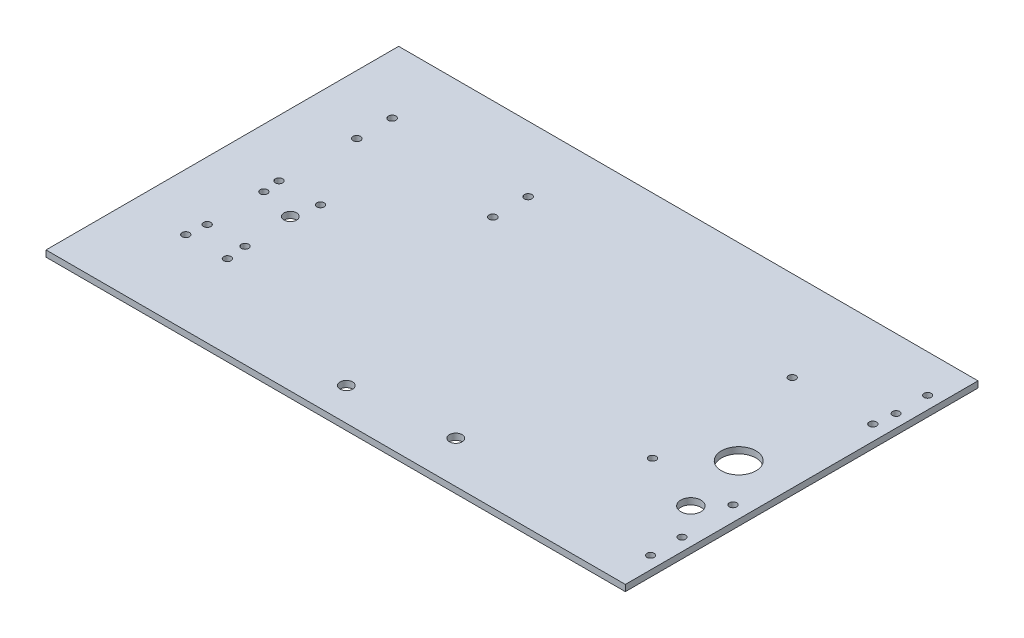
SolidWorks part; units mm, degrees
ref_plane "Front Plane" through (0, 0, 0) normal (0, 0, 1) x (1, 0, 0)
ref_plane "Top Plane" through (0, 0, 0) normal (0, 1, 0) x (1, 0, 0)
ref_plane "Right Plane" through (0, 0, 0) normal (1, 0, 0) x (0, 0, -1)
sketch "Sketch1" plane through (0, 0, 0) normal (0, 1, 0) x (1, 0, 0)
  line L1 (-158.75, 88.9) -> (158.75, 88.9)
  line L2 (-158.75, 88.9) -> (-158.75, -88.9)
  line L3 (-158.75, -88.9) -> (158.75, -88.9)
  line L4 (158.75, 88.9) -> (158.75, -88.9)
  line L5 (-158.75, 88.9) -> (158.75, -88.9) construction
  line L6 (-158.75, -88.9) -> (158.75, 88.9) construction
  circle A0 centre (-111.76, -12.7) radius 3.175
  circle A1 centre (107.95, -6.35) radius 8.7313
  circle A4 centre (-129.032, 55.88) radius 1.905
  circle A5 centre (-60.452, 55.88) radius 1.905
  circle A7 centre (-129.032, 38.1) radius 1.905
  circle A8 centre (-60.452, 38.1) radius 1.905
  point P0 (0, 0)
  dimension "D3" = 6.35
  dimension "D4" = 17.4625
  dimension "D14" = 3.81
  dimension "D17" = 17.78
  dimension "D1" = 317.5
  dimension "D2" = 177.8
  dimension "D5" = 46.99
  dimension "D6" = 266.7
  dimension "D7" = 95.25
  dimension "D8" = 76.2
  dimension "D13" = 29.718
  dimension "D15" = 68.58
  dimension "D16" = 127
extrude "Boss-Extrude1" add sketch "Sketch1" along normal blind 3.175
sketch "Sketch2" plane through (0, 3.175, 0) normal (0, 1, 0) x (1, 0, 0)
  line L0 (-158.75, 88.9) -> (-158.75, -88.9) construction
  line L1 (-158.75, -88.9) -> (158.75, -88.9) construction
  circle A0 centre (-89.0817, -33.177) radius 1.905
  circle A1 centre (-132.1376, -36.4483) radius 1.905
  dimension "D1" = 3.81
  dimension "D2" = 69.6683
  dimension "D3" = 52.4517
  dimension "D4" = 55.723
  dimension "D5" = 43.18
extrude "Cut-Extrude1" [suppressed] cut sketch "Sketch2" against normal through all
sketch "Sketch3" plane through (0, 0, 0) normal (0, -1, 0) x (-1, 0, 0)
  line L0 (158.75, -88.9) -> (-158.75, -88.9) construction
  line L1 (158.75, 88.9) -> (158.75, -88.9) construction
  circle A0 centre (23.8295, -72.39) radius 3.175
  circle A1 centre (-26.7643, -67.818) radius 3.175
  dimension "D1" = 6.35
  dimension "D2" = 4.572
  dimension "D3" = 16.51
  dimension "D4" = 185.5143
  dimension "D5" = 50.8
extrude "Cut-Extrude2" cut sketch "Sketch3" against normal through all
sketch "Sketch4" plane through (0, 3.175, 0) normal (0, 1, 0) x (1, 0, 0)
  line L0 (-158.75, -88.9) -> (158.75, -88.9) construction
  line L1 (158.75, 88.9) -> (133.35, 88.9)
  line L2 (158.75, 88.9) -> (158.75, -88.9)
  line L3 (158.75, -88.9) -> (133.35, -88.9)
  line L4 (133.35, 88.9) -> (133.35, -88.9)
  dimension "D1" = 25.4
extrude "Cut-Extrude3" cut sketch "Sketch4" against normal through all
sketch "Sketch5" plane through (0, 3.175, 0) normal (0, 1, 0) x (1, 0, 0)
  line L0 (133.35, 88.9) -> (-158.75, 88.9) construction
  line L1 (133.35, 88.9) -> (133.35, -88.9) construction
  circle A0 centre (115.57, -38.1) radius 5.08
  dimension "D3" = 10.16
  dimension "D1" = 127
  dimension "D2" = 17.78
extrude "Cut-Extrude4" cut sketch "Sketch5" against normal through all
sketch "Sketch6" plane through (0, 0, 0) normal (0, -1, 0) x (1, 0, 0)
  line L0 (-158.75, 88.9) -> (133.35, 88.9) construction
  line L1 (133.35, -88.9) -> (133.35, 88.9) construction
  line L2 (133.35, -88.9) -> (-158.75, -88.9) construction
  circle A0 centre (127, 69.85) radius 1.8034
  circle A2 centre (127, 53.975) radius 1.8034
  circle A3 centre (127, -53.975) radius 1.8034
  circle A4 centre (127, -69.85) radius 1.8034
  dimension "D4" = 3.6068
  dimension "D5" = 6.35
  dimension "D1" = 15.875
  dimension "D2" = 19.05
  dimension "D3" = 6.35
  dimension "D6" = 15.875
  dimension "D7" = 19.05
extrude "Cut-Extrude5" cut sketch "Sketch6" against normal through all
sketch "Sketch7" plane through (0, 3.175, 0) normal (0, 1, 0) x (1, 0, 0)
  line L0 (133.35, 88.9) -> (133.35, -88.9) construction
  line L1 (133.35, 88.9) -> (-158.75, 88.9) construction
  line L2 (-158.75, 88.9) -> (-158.75, -88.9) construction
  line L3 (-158.75, -88.9) -> (133.35, -88.9) construction
  circle A1 centre (125.73, 43.4975) radius 1.8415
  circle A2 centre (85.09, 43.4975) radius 1.8415
  circle A3 centre (85.09, -26.9875) radius 1.8415
  circle A4 centre (125.73, -26.9875) radius 1.8415
  circle A5 centre (-130.175, -46.99) radius 1.8415
  circle A6 centre (-109.22, -46.99) radius 1.8415
  circle A7 centre (-129.2225, -37.1475) radius 1.8415
  circle A8 centre (-110.1725, -37.1475) radius 1.8415
  circle A9 centre (-129.2225, -8.5725) radius 1.8415
  circle A10 centre (-130.175, 0) radius 1.8415
  circle A11 centre (-109.22, 0) radius 1.8415
  dimension "D1" = 7.62
  dimension "D5" = 3.683
  dimension "D10" = 3.683
  dimension "D15" = 3.683
  dimension "D2" = 40.64
  dimension "D3" = 70.485
  dimension "D4" = 61.9125
  dimension "D6" = 28.575
  dimension "D7" = 20.955
  dimension "D8" = 0.9525
  dimension "D9" = 19.05
  dimension "D11" = 88.9
  dimension "D12" = 8.5725
  dimension "D13" = 28.575
  dimension "D14" = 9.8425
extrude "Cut-Extrude6" cut sketch "Sketch7" against normal through all
